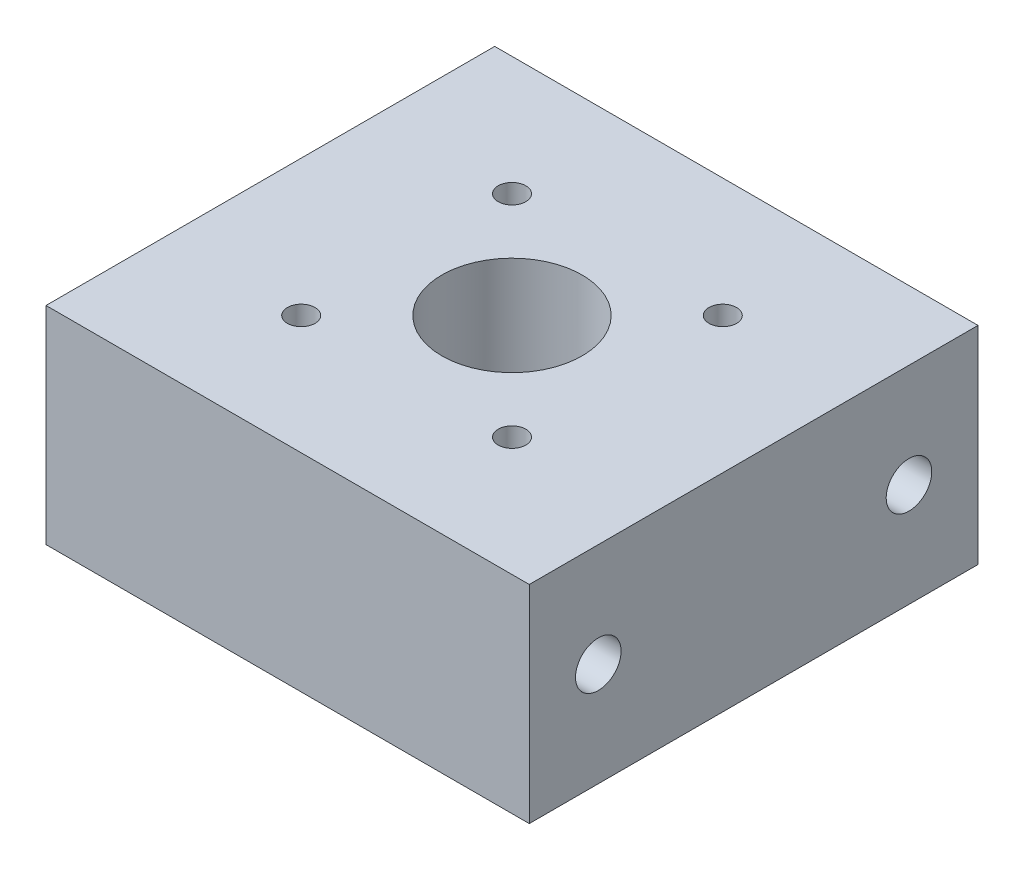
SolidWorks part; units mm, degrees
ref_plane "Front Plane" through (0, 0, 0) normal (0, 0, 1) x (1, 0, 0)
ref_plane "Top Plane" through (0, 0, 0) normal (0, 1, 0) x (1, 0, 0)
ref_plane "Right Plane" through (0, 0, 0) normal (1, 0, 0) x (0, 0, -1)
sketch "Sketch1" plane through (0, 0, 0) normal (0, 1, 0) x (1, 0, 0)
  line L1 (-17.5, -16.25) -> (17.5, -16.25)
  line L2 (-17.5, -16.25) -> (-17.5, 16.25)
  line L3 (-17.5, 16.25) -> (17.5, 16.25)
  line L4 (17.5, -16.25) -> (17.5, 16.25)
  line L5 (-17.5, -16.25) -> (17.5, 16.25) construction
  line L6 (-17.5, 16.25) -> (17.5, -16.25) construction
  point P0 (0, 0)
  dimension "D1" = 35
  dimension "D2" = 32.5
extrude "Boss-Extrude1" add sketch "Sketch1" against normal blind 15
sketch "Sketch2" plane through (0, 0, 0) normal (0, 1, 0) x (1, 0, 0)
  circle A0 centre (0, 0) radius 5.08
  dimension "D2" = 10.16
extrude "Cut-Extrude2" cut sketch "Sketch2" against normal blind 30
sketch "Sketch4" plane through (0, 0, 0) normal (0, 1, 0) x (1, 0, 0)
  line L0 (7.633, 7.633) -> (7.633, 0) construction
  line L1 (7.633, 0) -> (0, 0) construction
  line L2 (0, 0) -> (-7.633, 0) construction
  line L3 (-7.633, 0) -> (-7.633, 7.633) construction
  line L4 (7.633, 0) -> (7.633, -7.633) construction
  line L5 (-7.633, 0) -> (-7.633, -7.633) construction
  circle A0 centre (7.633, 7.633) radius 1
  circle A1 centre (-7.633, 7.633) radius 1
  circle A2 centre (-7.633, -7.633) radius 1
  circle A3 centre (7.633, -7.633) radius 1
  dimension "D2" = 2
  dimension "D1" = 7.633
extrude "Cut-Extrude3" cut sketch "Sketch4" against normal blind 14.7
hole_wizard "M4x0.7 Tapped Hole1" positions "Sketch6" profile "Sketch5" tap size "M4x0.7" standard "ANSI Metric" end condition through all
sketch "Sketch6" plane through (-17.5, 0, 0) normal (1, 0, 0) x (0, -1, 0)
  line L1 (7.5, 16.25) -> (7.5, -16.25) construction
  line L2 (15, 16.25) -> (0, 16.25) construction
  line L3 (15, -16.25) -> (0, -16.25) construction
  point P0 (7.5, 11.25)
  point P2 (7.5, -11.25)
  dimension "D1" = 5
  dimension "D2" = 5
sketch "Sketch5" plane through (-17.5, -7.5, -11.25) normal (0, 1, 0) x (0, 0, 1)
  line L0 (0, 0) -> (0, 35)
  line L1 (0, 35) -> (1.65, 35)
  line L2 (1.65, 35) -> (1.65, 0)
  line L5 (1.65, 0) -> (0, 0)
  line L11 (0, -6.35) -> (0, 107.95) construction
  dimension "Thru Tap Drill Dia." = 3.3
  dimension "Thru Tap Drill Depth" = 35
cosmetic thread "Hole Thread1" parameters "D2"=4
cosmetic thread "Hole Thread2" parameters "D2"=4
